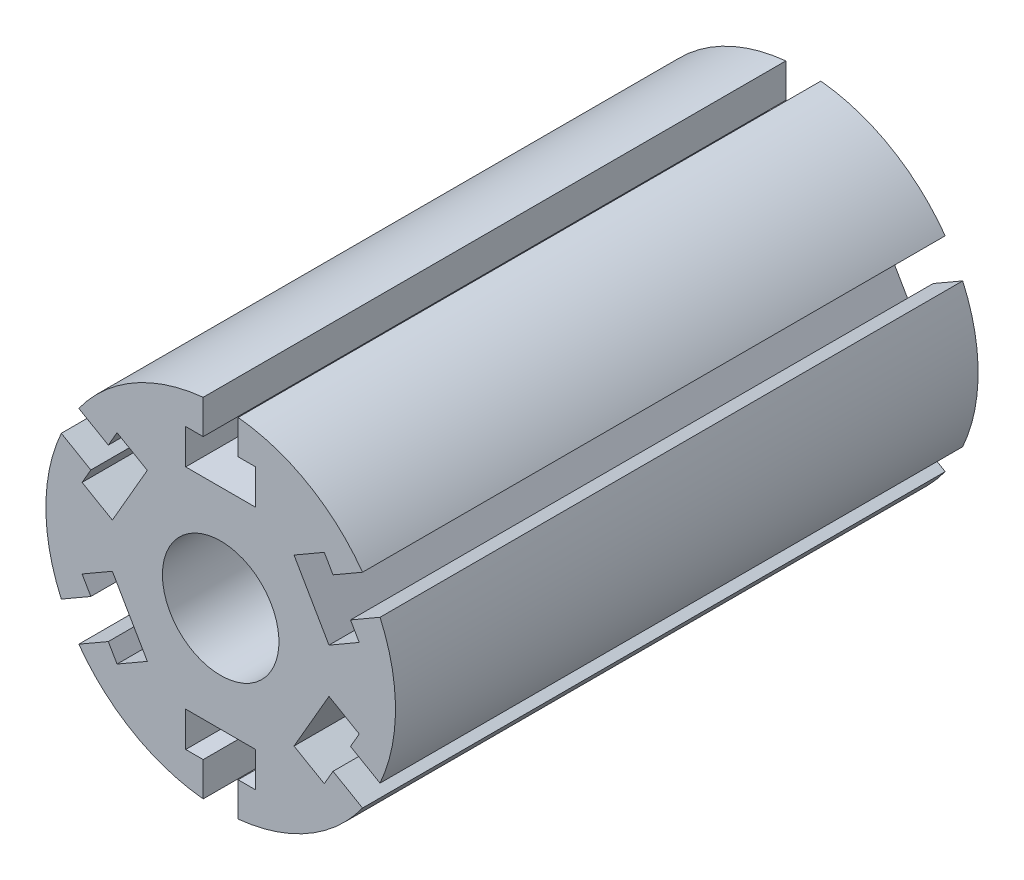
SolidWorks part; units mm, degrees
other "Marcação1"
sketch "Esboço6" plane through (-5, 5.7735, 12.5) normal (-0.9372, 0.3304, 0.1115) x (0.1181, 0, 0.993)
ref_plane "Plano frontal" through (0, 0, 0) normal (0, 0, 1) x (1, 0, 0)
ref_plane "Plano superior" through (0, 0, 0) normal (0, 1, 0) x (1, 0, 0)
ref_plane "Plano direito" through (0, 0, 0) normal (1, 0, 0) x (0, 0, -1)
sketch "Esboço1" plane through (0, 0, 0) normal (0, 0, 1) x (1, 0, 0)
  circle A0 centre (0, 0) radius 2.5 construction
  circle A2 centre (0, 0) radius 7.5
  dimension "D1" = 5
  dimension "D2" = 15
extrude "Ressalto-extrusão1" add sketch "Esboço1" along normal mid plane 25
sketch "Esboço7" plane through (0, 0, 12.5) normal (0, 0, -1) x (-1, 0, 0)
  circle A0 centre (0, 0) radius 2.5
  dimension "D1" = 5
extrude "Corte-extrusão1" cut sketch "Esboço7" along normal blind 16
sketch "Esboço9" plane through (0, 0, 12.5) normal (0, 0, 1) x (1, 0, 0)
  line L0 (-0.75, 6) -> (-0.75, 7.5)
  line L1 (-0.75, 7.5) -> (0.75, 7.5)
  line L2 (-1.5, 6) -> (-0.75, 6)
  line L3 (-1.5, 6) -> (-1.5, 4.5)
  line L4 (-1.5, 4.5) -> (1.5, 4.5)
  line L5 (1.5, 6) -> (1.5, 4.5)
  line L6 (0.75, 6) -> (1.5, 6)
  line L7 (0.75, 6) -> (0.75, 7.5)
  line L8 (4.4462, 4.299) -> (3.1471, 3.549)
  line L9 (4.4462, 4.299) -> (4.8212, 3.6495)
  line L10 (4.8212, 3.6495) -> (6.1202, 4.3995)
  line L11 (6.1202, 4.3995) -> (6.8702, 3.1005)
  line L12 (5.5712, 2.3505) -> (6.8702, 3.1005)
  line L13 (5.5712, 2.3505) -> (5.9462, 1.701)
  line L14 (5.9462, 1.701) -> (4.6471, 0.951)
  line L15 (3.1471, 3.549) -> (4.6471, 0.951)
  line L16 (5.9462, -1.701) -> (4.6471, -0.951)
  line L17 (5.9462, -1.701) -> (5.5712, -2.3505)
  line L18 (5.5712, -2.3505) -> (6.8702, -3.1005)
  line L19 (6.8702, -3.1005) -> (6.1202, -4.3995)
  line L20 (4.8212, -3.6495) -> (6.1202, -4.3995)
  line L21 (4.8212, -3.6495) -> (4.4462, -4.299)
  line L22 (4.4462, -4.299) -> (3.1471, -3.549)
  line L23 (4.6471, -0.951) -> (3.1471, -3.549)
  line L24 (1.5, -6) -> (1.5, -4.5)
  line L25 (1.5, -6) -> (0.75, -6)
  line L26 (0.75, -6) -> (0.75, -7.5)
  line L27 (0.75, -7.5) -> (-0.75, -7.5)
  line L28 (-0.75, -6) -> (-0.75, -7.5)
  line L29 (-0.75, -6) -> (-1.5, -6)
  line L30 (-1.5, -6) -> (-1.5, -4.5)
  line L31 (1.5, -4.5) -> (-1.5, -4.5)
  line L32 (-4.4462, -4.299) -> (-3.1471, -3.549)
  line L33 (-4.4462, -4.299) -> (-4.8212, -3.6495)
  line L34 (-4.8212, -3.6495) -> (-6.1202, -4.3995)
  line L35 (-6.1202, -4.3995) -> (-6.8702, -3.1005)
  line L36 (-5.5712, -2.3505) -> (-6.8702, -3.1005)
  line L37 (-5.5712, -2.3505) -> (-5.9462, -1.701)
  line L38 (-5.9462, -1.701) -> (-4.6471, -0.951)
  line L39 (-3.1471, -3.549) -> (-4.6471, -0.951)
  line L40 (-5.9462, 1.701) -> (-4.6471, 0.951)
  line L41 (-5.9462, 1.701) -> (-5.5712, 2.3505)
  line L42 (-5.5712, 2.3505) -> (-6.8702, 3.1005)
  line L43 (-6.8702, 3.1005) -> (-6.1202, 4.3995)
  line L44 (-4.8212, 3.6495) -> (-6.1202, 4.3995)
  line L45 (-4.8212, 3.6495) -> (-4.4462, 4.299)
  line L46 (-4.4462, 4.299) -> (-3.1471, 3.549)
  line L47 (-4.6471, 0.951) -> (-3.1471, 3.549)
  circle A0 centre (0, 0) radius 7.5 construction
  point P7 (0, 7.5)
  point P55 (0, 0)
  dimension "D1" = 1.5
  dimension "D2" = 3
  dimension "D3" = 3
  dimension "D4" = 1.5
  dimension "D5" = 6
extrude "Corte-extrusão2" cut sketch "Esboço9" against normal through all
